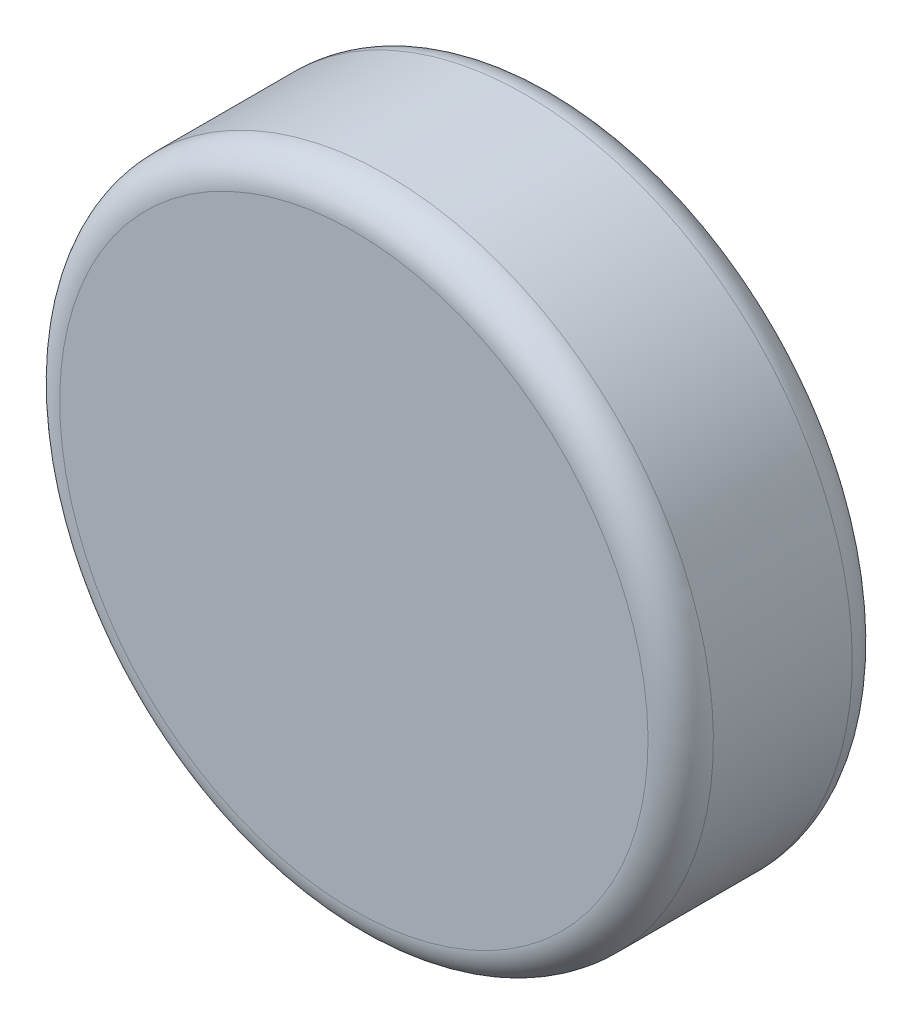
SolidWorks part; units mm, degrees
ref_plane "Front Plane" through (0, 0, 0) normal (0, 0, 1) x (1, 0, 0)
ref_plane "Top Plane" through (0, 0, 0) normal (0, 1, 0) x (1, 0, 0)
ref_plane "Right Plane" through (0, 0, 0) normal (1, 0, 0) x (0, 0, -1)
sketch "Sketch1" plane through (0, 0, 15.395) normal (0, 0, -1) x (-1, 0, 0)
  circle A0 centre (4.95, -15.4) radius 4 construction
  circle A1 centre (4.95, -15.4) radius 4
extrude "Boss-Extrude1" add sketch "Sketch1" along normal blind 2.5
fillet "Fillet1" radius 0.4 2 edges at (-4.95, -11.4, 15.395) (-4.95, -11.4, 12.895)
